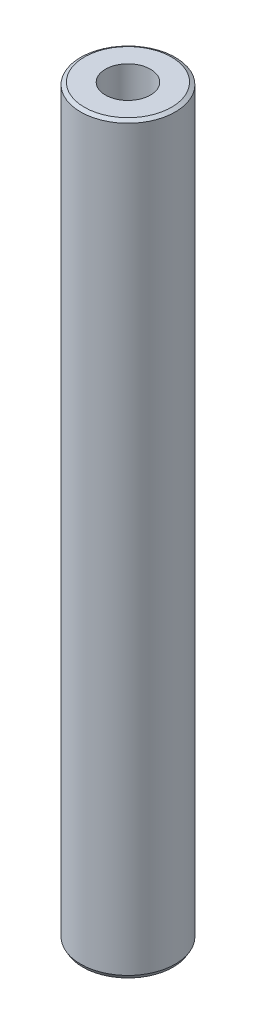
SolidWorks part; units mm, degrees
ref_plane "Front Plane" through (0, 0, 0) normal (0, 0, 1) x (1, 0, 0)
ref_plane "Top Plane" through (0, 0, 0) normal (0, 1, 0) x (1, 0, 0)
ref_plane "Right Plane" through (0, 0, 0) normal (1, 0, 0) x (0, 0, -1)
sketch "Sketch1" plane through (0, 0, 0) normal (0, 1, 0) x (1, 0, 0)
  circle A0 centre (0, 0) radius 7.5
  dimension "SHAFT_OD" = 15
extrude "Boss-Extrude1" add sketch "Sketch1" along normal blind 117.8832
sketch "Sketch2" plane through (0, 0, 0) normal (0, 1, 0) x (1, 0, 0)
  circle A0 centre (0, 0) radius 3.5626
  dimension "BORE_D" = 7.1252
extrude "Cut-Extrude1" cut sketch "Sketch2" along normal through all
chamfer "Chamfer1" distance 0.3442 angle 60 2 edges at (0, 117.8832, 7.5) (0, 0, 7.5) first distance on face at (0, 117.8832, 7.5) first distance on face at (0, 0, 3.5626)
